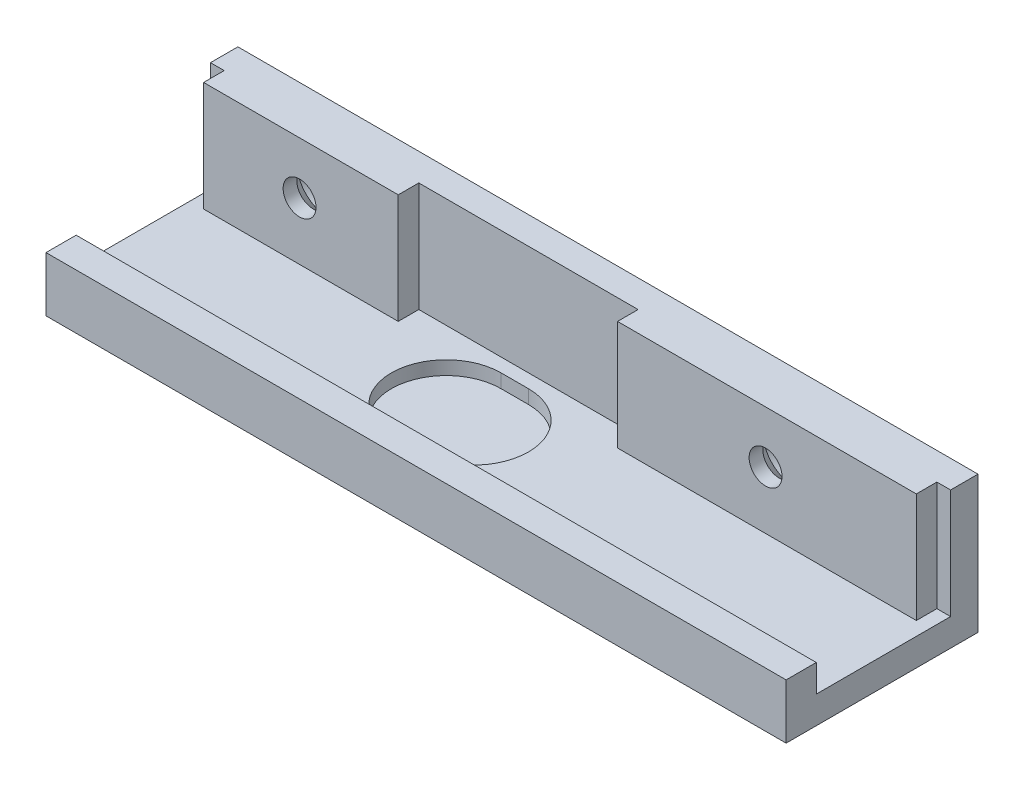
SolidWorks part; units mm, degrees
ref_plane "Front Plane" through (0, 0, 0) normal (0, 0, 1) x (1, 0, 0)
ref_plane "Top Plane" through (0, 0, 0) normal (0, 1, 0) x (1, 0, 0)
ref_plane "Right Plane" through (0, 0, 0) normal (1, 0, 0) x (0, 0, -1)
sketch "Sketch2" plane through (0, 0, 0) normal (0, 1, 0) x (1, 0, 0)
  line L1 (0, 0) -> (68.58, 0)
  line L2 (0, 0) -> (0, -17.78)
  line L3 (0, -17.78) -> (68.58, -17.78)
  line L4 (68.58, 0) -> (68.58, -17.78)
  dimension "D1" = 17.78
  dimension "D2" = 68.58
extrude "Boss-Extrude1" add sketch "Sketch2" along normal blind 2.54
sketch "Sketch3" plane through (0, 2.54, 0) normal (0, 1, 0) x (1, 0, 0)
  line L0 (68.58, -17.78) -> (68.58, 0) construction
  line L1 (0, -17.78) -> (68.58, -17.78)
  line L2 (0, -17.78) -> (0, -15.24)
  line L3 (0, -15.24) -> (68.58, -15.24)
  line L4 (68.58, -17.78) -> (68.58, -15.24)
  dimension "D1" = 2.54
extrude "Boss-Extrude2" add sketch "Sketch3" along normal blind 2.54
sketch "Sketch4" plane through (0, 2.54, 0) normal (0, 1, 0) x (1, 0, 0)
  line L0 (68.58, -15.24) -> (68.58, 0) construction
  line L1 (0, 0) -> (68.58, 0)
  line L2 (0, 0) -> (0, -2.54)
  line L3 (0, -2.54) -> (1.27, -2.54)
  line L4 (68.58, 0) -> (68.58, -2.54)
  line L5 (19.304, -2.54) -> (39.624, -2.54)
  line L6 (67.31, -2.54) -> (68.58, -2.54)
  line L7 (1.27, -2.54) -> (1.27, -4.445)
  line L8 (1.27, -4.445) -> (19.304, -4.445)
  line L9 (19.304, -2.54) -> (19.304, -4.445)
  line L10 (68.58, -15.24) -> (0, -15.24) construction
  line L11 (39.624, -2.54) -> (39.624, -4.445)
  line L12 (39.624, -4.445) -> (67.31, -4.445)
  line L13 (67.31, -2.54) -> (67.31, -4.445)
  line L14 (1.27, -4.445) -> (0, -4.445) construction
  line L15 (0, 0) -> (0, -15.24) construction
  line L16 (67.31, -4.445) -> (68.58, -4.445) construction
  point P17 (41.551, -6.985)
  dimension "D1" = 12.7
  dimension "D2" = 10.795
  dimension "D3" = 20.32
  dimension "D4" = 66.04
  dimension "D5" = 27.686
extrude "Boss-Extrude3" add sketch "Sketch4" along normal blind 10.16 contours L9 L8 L7 L3 L2 L1 L4 L6 L13 L12 L11 L5
sketch "Sketch5" plane through (0, 0, 4.445) normal (0, 0, 1) x (1, 0, 0)
  line L0 (39.624, 2.54) -> (67.31, 2.54) construction
  line L2 (39.624, 12.7) -> (39.624, 2.54) construction
  circle A0 centre (10.16, 7.874) radius 1.524
  circle A1 centre (53.34, 7.874) radius 1.524
  point P6 (11.5752, 8.5409)
  point P7 (0, 0)
  dimension "D1" = 3.048
  dimension "D2" = 5.334
  dimension "D3" = 43.18
  dimension "D4" = 13.716
extrude "Cut-Extrude1" cut sketch "Sketch5" against normal through all
sketch "Sketch6" plane through (0, 0, 4.445) normal (0, 0, 1) x (1, 0, 0)
  circle A0 centre (10.16, 7.874) radius 2.921
  circle A1 centre (53.34, 7.874) radius 2.921
  dimension "D1" = 5.842
extrude "Cut-Extrude2" cut sketch "Sketch6" against normal through all from offset 3.81 offset against normal yes
chamfer "Chamfer1" distance 2.54 angle 45 2 edges at (54.864, 7.874, 0.635) (11.684, 7.874, 0.635)
sketch "Sketch7" plane through (0, 2.54, 0) normal (0, 1, 0) x (1, 0, 0)
  line L0 (28.194, -8.89) -> (30.734, -8.89) construction
  line L1 (28.194, -3.81) -> (30.734, -3.81)
  line L2 (28.194, -13.97) -> (30.734, -13.97)
  line L3 (19.304, -2.54) -> (39.624, -2.54) construction
  line L4 (29.464, -2.54) -> (29.464, -15.24) construction
  line L5 (68.58, -15.24) -> (0, -15.24) construction
  arc A0 (28.194, -3.81) -> (28.194, -13.97) centre (28.194, -8.89) ccw
  arc A1 (30.734, -13.97) -> (30.734, -3.81) centre (30.734, -8.89) ccw
  point P2 (29.464, -8.89)
  point P10 (29.464, -2.54)
  point P14 (28.194, -10.3132)
  point P15 (0, 0)
  point P16 (29.464, -8.89)
  dimension "D1" = 10.16
  dimension "D2" = 2.54
extrude "Cut-Extrude3" cut sketch "Sketch7" against normal blind 1.27
sketch "Sketch8" plane through (0, 0, 15.24) normal (0, 0, -1) x (-1, 0, 0)
  line L1 (0, 2.54) -> (-68.58, 2.54)
  line L2 (0, 2.54) -> (0, 5.08)
  line L3 (0, 5.08) -> (-68.58, 5.08)
  line L4 (-68.58, 2.54) -> (-68.58, 5.08)
extrude "Extra_width_for_mirrored_part" add sketch "Sketch8" along normal blind 0.254
